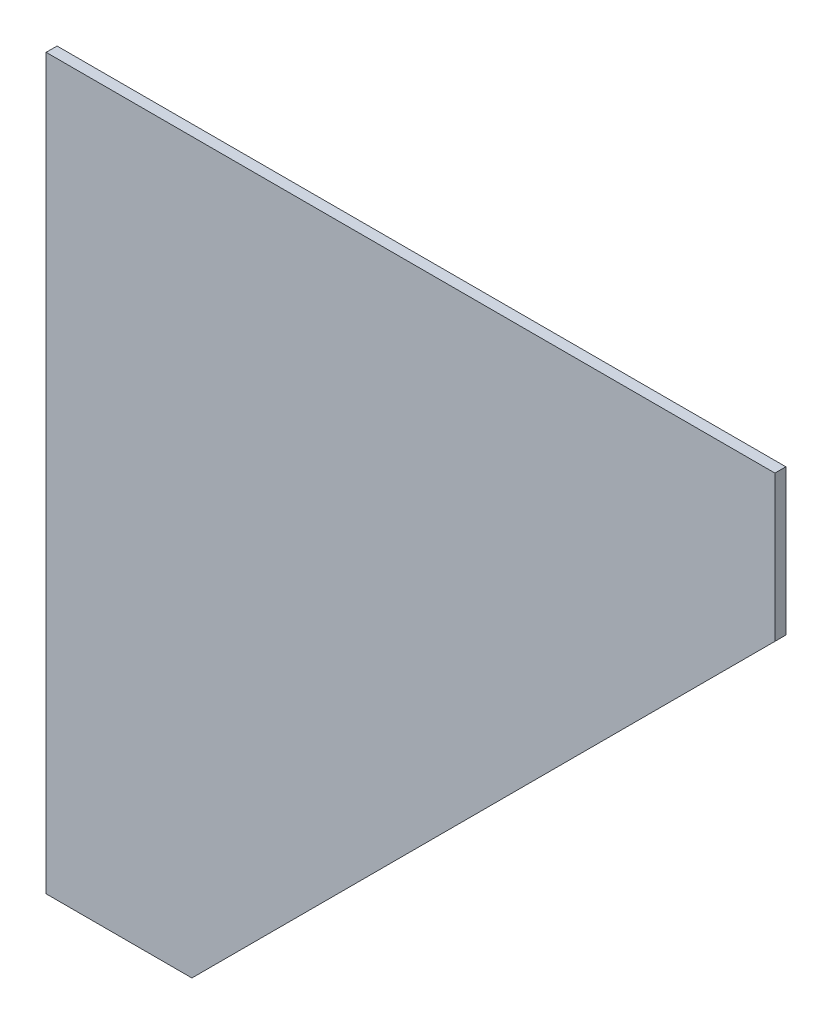
SolidWorks part; units mm, degrees
ref_plane "Piano frontale" through (0, 0, 0) normal (0, 0, 1) x (1, 0, 0)
ref_plane "Piano superiore" through (0, 0, 0) normal (0, 1, 0) x (1, 0, 0)
ref_plane "Piano destro" through (0, 0, 0) normal (1, 0, 0) x (0, 0, -1)
sketch "Schizzo1" plane through (0, 0, 0) normal (0, 0, 1) x (1, 0, 0)
  line L0 (0, 0) -> (0, 200)
  line L1 (0, 200) -> (200, 200)
  line L2 (200, 200) -> (200, 160)
  line L3 (200, 160) -> (40, 0)
  line L4 (40, 0) -> (0, 0)
  point P6 (200, 180)
  dimension "D1" = 45
  dimension "D2" = 40
  dimension "D3" = 200
  dimension "D4" = 200
extrude "Estrusione-Estrusione1" add sketch "Schizzo1" along normal blind 3
